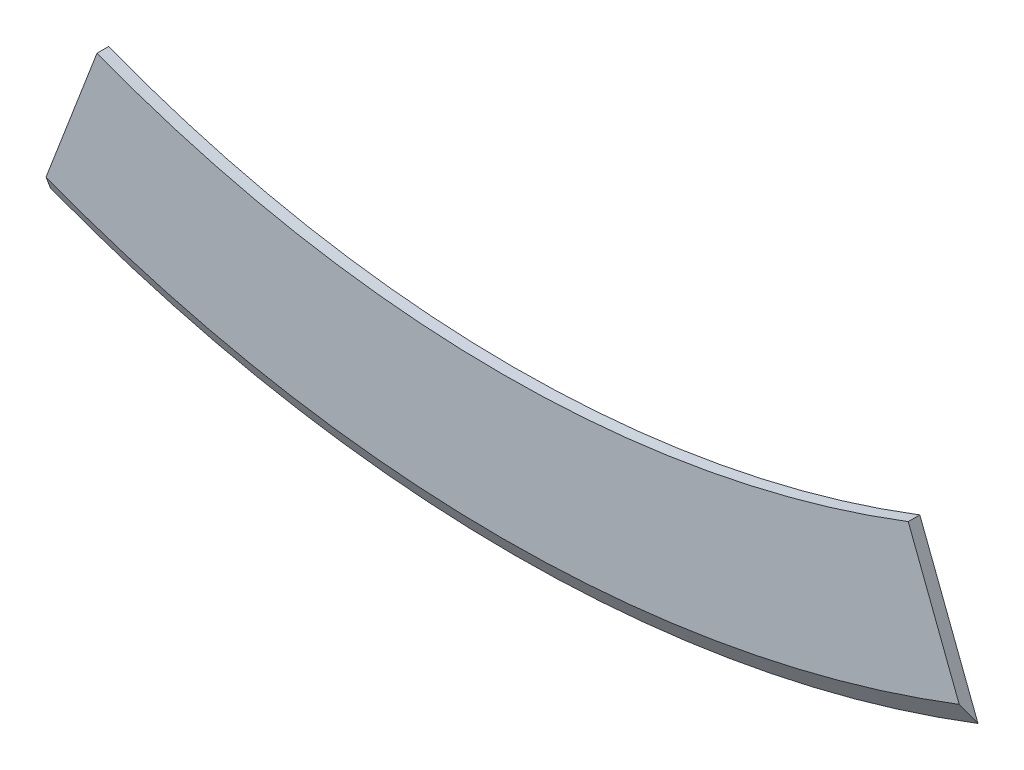
SolidWorks part; units mm, degrees
ref_plane "Plan de face" through (0, 0, 0) normal (0, 0, 1) x (1, 0, 0)
ref_plane "Plan de dessus" through (0, 0, 0) normal (0, 1, 0) x (1, 0, 0)
ref_plane "Plan de droite" through (0, 0, 0) normal (1, 0, 0) x (0, 0, -1)
sketch "Esquisse1" plane through (0, 0, 0) normal (0, 0, 1) x (1, 0, 0)
  line L0 (0, 0) -> (0, 42) construction
  line L1 (-104.9485, 61.4511) -> (104.9485, 61.4511) construction
  line L2 (120, 22.2407) -> (-120, 22.2407) construction
  line L3 (-120, 22.2407) -> (-104.9485, 61.4511)
  line L4 (120, 22.2407) -> (104.9485, 61.4511)
  line L5 (104.9485, 61.4511) -> (0, 334.8514) construction
  line L6 (0, 334.8514) -> (-104.9485, 61.4511) construction
  arc A0 (-104.9485, 61.4511) -> (104.9485, 61.4511) centre (0, 334.8514) ccw
  arc A1 (-120, 22.2407) -> (120, 22.2407) centre (0, 334.8514) ccw
  dimension "D1" = 42
  dimension "D2" = 240
  dimension "D3" = 42
extrude "Boss.-Extru.1" add sketch "Esquisse1" along normal blind 3
chamfer "Chanfrein1" distance 3 angle 60 1 edges at (0, 0, 3) first distance on face at (0, 11.1203, 1.5)
